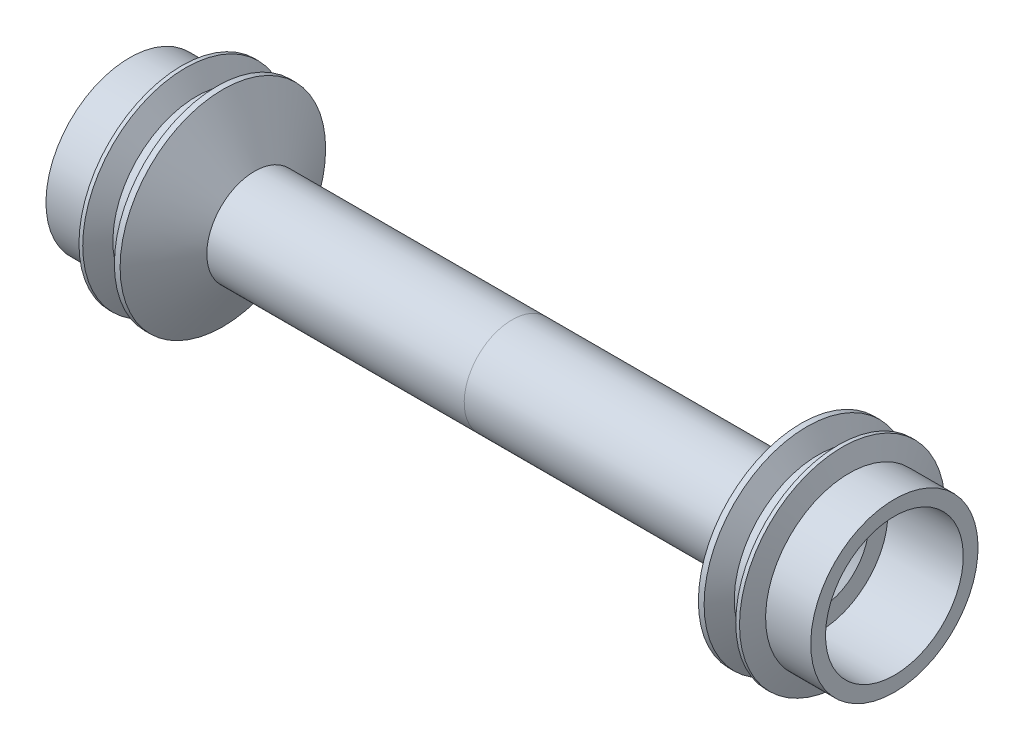
SolidWorks part; units mm, degrees
ref_plane "Front Plane" through (0, 0, 0) normal (0, 0, 1) x (1, 0, 0)
ref_plane "Top Plane" through (0, 0, 0) normal (0, 1, 0) x (1, 0, 0)
ref_plane "Right Plane" through (0, 0, 0) normal (1, 0, 0) x (0, 0, -1)
sketch "Sketch2" plane through (0, 0, 0) normal (0, 0, 1) x (1, 0, 0)
  line L0 (0, 0) -> (0, 28.4375) construction
  line L1 (-25.4, 4.575) -> (-20.4, 4.575) construction
  line L2 (-25.4, 4.575) -> (-25.4, -4.575) construction
  line L3 (-25.4, -4.575) -> (-20.4, -4.575) construction
  line L4 (-20.4, 4.575) -> (-20.4, -4.575) construction
  line L5 (-25.4, 4.575) -> (-20.4, -4.575) construction
  line L6 (-25.4, -4.575) -> (-20.4, 4.575) construction
  line L7 (20.4, 4.5) -> (43.1832, 4.5) construction
  line L8 (20.4, 4.5) -> (20.4, -4.5) construction
  line L9 (20.4, -4.5) -> (43.1832, -4.5) construction
  line L10 (43.1832, 4.5) -> (43.1832, -4.5) construction
  line L11 (20.4, 4.5) -> (43.1832, -4.5) construction
  line L12 (20.4, -4.5) -> (43.1832, 4.5) construction
  line L13 (-25.4, 0) -> (43.1832, 0) construction
  line L14 (-25.4, 5.5562) -> (-22.4, 5.5562)
  line L15 (-22.4, 5.5562) -> (-21.9378, 6.8262)
  line L16 (-21.9378, 6.8262) -> (-21.6882, 6.8262)
  line L19 (-19.5868, 6.8262) -> (-19.2058, 6.8262)
  line L20 (-19.2058, 6.8262) -> (-17.0977, 3.175)
  line L21 (-17.0977, 3.175) -> (0, 3.175)
  line L22 (-25.4, 5.5562) -> (-25.4, 4.575)
  line L23 (-25.4, 4.575) -> (-20.4, 4.575)
  line L24 (-20.4, 4.575) -> (-20.4, 0)
  line L25 (-20.4, 0) -> (0, 0)
  line L26 (0, 0) -> (0, 3.175)
  line L27 (-33.5594, -5.5562) -> (-33.5594, 5.5562) construction
  line L28 (-20.6375, 5.5562) -> (-20.6375, 7.68) construction
  line L29 (-20.6375, 5.5562) -> (20.6375, 5.5562) construction
  line L30 (-25.4, 5.5562) -> (25.4, 5.5562) construction
  line L31 (0, 1.6) -> (-12.5, 1.6)
  line L32 (-12.5, 1.6) -> (-14.1, 0)
  line L33 (-12.5, 1.6) -> (-12.5, -1.6) construction
  line L34 (-12.5, 1.6) -> (12.5, 1.6) construction
  line L35 (-20.4, 1.7145) -> (-15.575, 1.7145)
  line L36 (-15.575, 1.7145) -> (-15.575, 0)
  line L37 (-20.4, 3.305) -> (-19.892, 2.797)
  line L38 (-15.575, 1.7145) -> (-28.575, 1.7145) construction
  line L39 (-15.575, 1.7145) -> (-15.575, -1.7145) construction
  line L40 (-15.575, -1.7145) -> (-28.575, -1.7145) construction
  line L41 (-28.575, 1.7145) -> (-28.575, -1.7145) construction
  line L42 (-19.892, 2.797) -> (-19.892, 0)
  line L43 (-20.955, 5.5562) -> (-20.32, 5.5562)
  line L44 (-20.32, 5.5562) -> (-19.5868, 6.8262)
  line L45 (-21.6882, 6.8262) -> (-20.955, 5.5562)
  point P0 (-22.9, 0)
  point P5 (31.7916, 0)
  point P27 (-33.5594, 0)
  point P28 (-19.3963, 6.8262)
  point P29 (-12.5, 0)
  point P33 (0, 5.5562)
  point P36 (0, 1.6)
  point P48 (-15.575, 0)
  point P51 (0, 5.5562)
  point P53 (0, 0)
  point P54 (-20.6375, 5.5562)
  dimension "D1" = 5
  dimension "D3" = 3.175
  dimension "D4" = 11.1125
  dimension "D5" = 9.15
  dimension "D6" = 60
  dimension "D7" = 60
  dimension "D8" = 1.27
  dimension "D9" = 70
  dimension "D10" = 41.275
  dimension "D11" = 50.8
  dimension "D12" = 0.381
  dimension "D13" = 45
  dimension "D14" = 25
  dimension "D15" = 3.2
  dimension "D16" = 3.429
  dimension "D17" = 3.175
  dimension "D18" = 1.27
  dimension "D19" = 0.508
  dimension "D20" = 45
  dimension "D21" = 13
  dimension "D22" = 3
  dimension "D23" = 0.635
revolve "Revolve1" add sketch "Sketch2" angle 360 about L13 region at (-13.2542, 2.9873, 0)
mirror "Mirror1" about plane through (0, 0, 0) normal (1, 0, 0) of bodies 101
chamfer "Chamfer1" distance 0.508 angle 45 1 edges at (-25.4, -4.575, 0)
